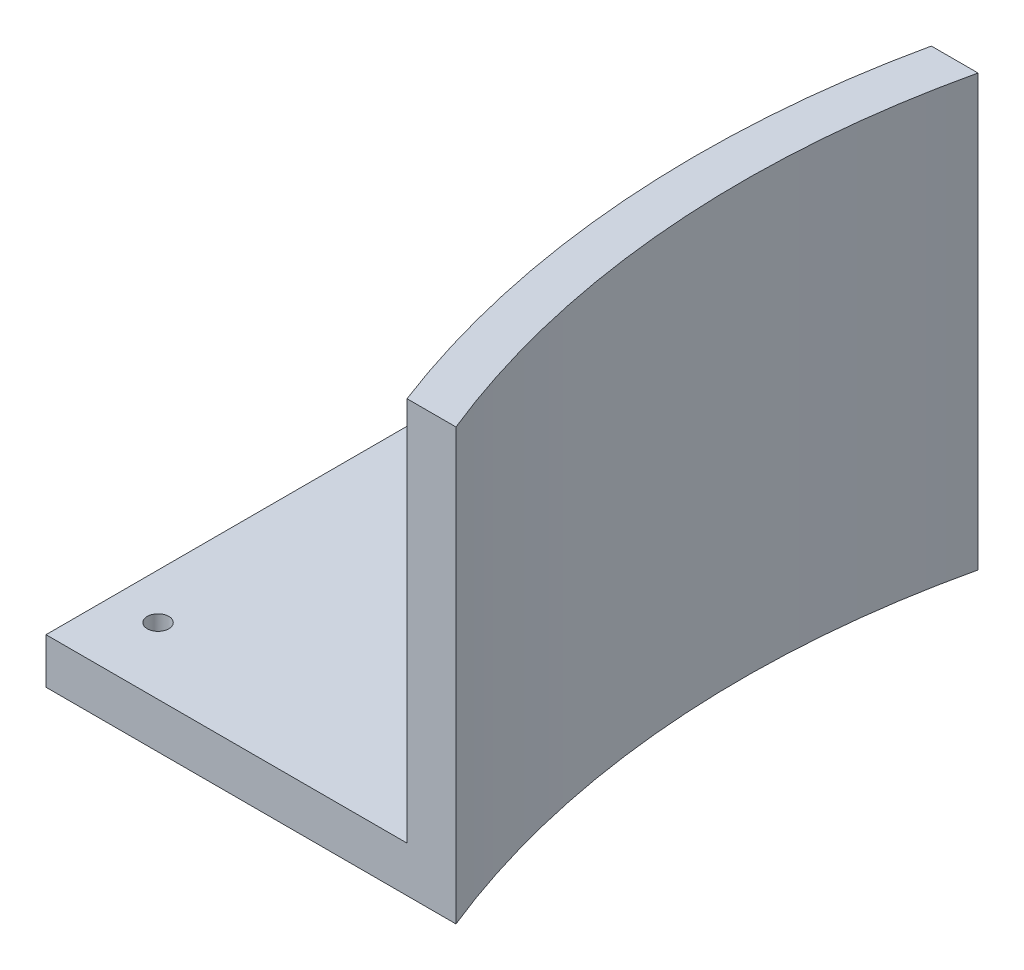
SolidWorks part; units mm, degrees
ref_plane "Front Plane" through (0, 0, 0) normal (0, 0, 1) x (1, 0, 0)
ref_plane "Top Plane" through (0, 0, 0) normal (0, 1, 0) x (1, 0, 0)
ref_plane "Right Plane" through (0, 0, 0) normal (1, 0, 0) x (0, 0, -1)
sketch "Sketch1" plane through (0, 0, 0) normal (0, 1, 0) x (1, 0, 0)
  line L0 (50.8, 79.121) -> (0, 79.121)
  line L1 (0, 79.121) -> (0, 0)
  line L2 (0, 0) -> (57.15, 0)
  arc A1 (50.8, 79.121) -> (57.15, 0) centre (179.5475, 49.6385) ccw
  dimension "D2" = 264.16
  dimension "D3" = 79.121
  dimension "D4" = 57.15
extrude "Boss-Extrude1" add sketch "Sketch1" along normal blind 60
sketch "Sketch3" plane through (0, 0, 0) normal (0, 1, 0) x (1, 0, 0)
  line L0 (51.2655, -2.3865) -> (0, 0)
  line L2 (0, 0) -> (0, 79.121)
  line L3 (0, 79.121) -> (44.2935, 79.121)
  line L5 (50.8, 79.121) -> (0, 79.121) construction
  arc A3 (44.6102, 80.5384) -> (51.2655, -2.3865) centre (179.5475, 49.6385) ccw
  arc A4 (44.2935, 79.121) -> (51.2655, -2.3865) centre (179.5475, 49.6385) ccw
  dimension "D1" = 6.35
extrude "Cut-Extrude1" cut sketch "Sketch3" against normal offset from surface (53.65 mm away) 6.35 from surface up to face at (25.4665, 0, -39.4384) starting at face at (25.4665, 60, -39.4384)
sketch "Sketch4" plane through (0, 6.35, 0) normal (0, 1, 0) x (1, 0, 0)
  line L0 (44.2935, 79.121) -> (0, 79.121) construction
  line L1 (0, 79.121) -> (0, 0) construction
  circle A0 centre (6.35, 72.771) radius 1.5
  circle A1 centre (25.4, 72.771) radius 1.5
  circle A3 centre (6.35, 9.271) radius 1.5
  circle A4 centre (25.4, 9.271) radius 1.5 [skipped]
  dimension "D1" = 3
  dimension "D2" = 6.35
  dimension "D3" = 6.35
  dimension "D5" = 2
extrude "Cut-Extrude2" cut sketch "Sketch4" against normal through all
equation "\"tightTol\" = 0.005in"
equation "\"normTol\"= 0.01in"
equation "\"looseTol\"= 0.02in"
equation "\"D3@Sketch1\"=3.125000in-\"normTol\""
equation "\"D1@Sketch4\"=3mm"
equation "\"D1@Boss-Extrude1\"=60mm"
